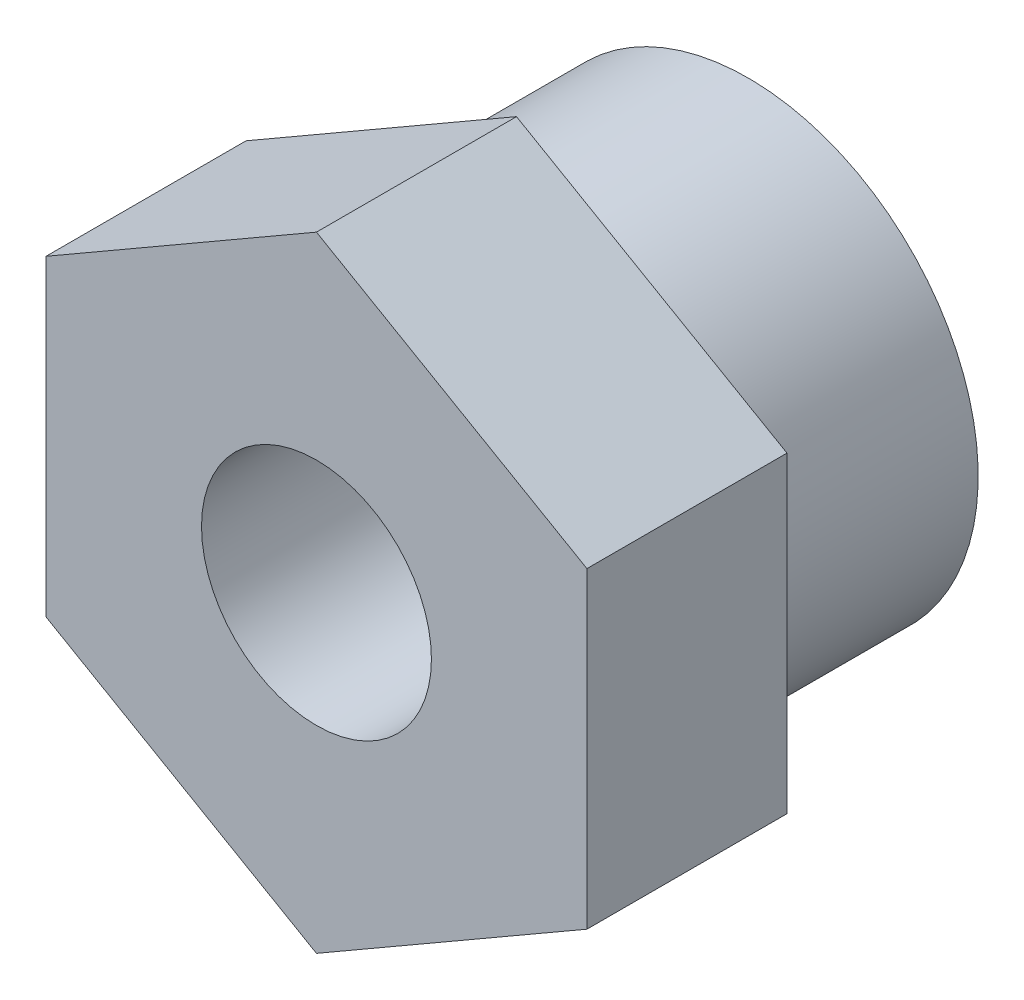
SolidWorks part; units mm, degrees
ref_plane "Piano frontale" through (0, 0, 0) normal (0, 0, 1) x (1, 0, 0)
ref_plane "Piano superiore" through (0, 0, 0) normal (0, 1, 0) x (1, 0, 0)
ref_plane "Piano destro" through (0, 0, 0) normal (1, 0, 0) x (0, 0, -1)
sketch "Schizzo1" plane through (0, 0, 0) normal (0, 0, 1) x (1, 0, 0)
  circle A0 centre (0, 0) radius 17.25
  dimension "D1" = 34.5
extrude "Estrusione-Estrusione1" add sketch "Schizzo1" along normal blind 23.85
sketch "Schizzo2" plane through (0, 0, 23.85) normal (0, 0, 1) x (1, 0, 0)
  line L1 (0, 17.25) -> (-14.9389, 8.625)
  line L2 (-14.9389, 8.625) -> (-14.9389, -8.625)
  line L3 (-14.9389, -8.625) -> (0, -17.25)
  line L4 (0, -17.25) -> (14.9389, -8.625)
  line L5 (14.9389, -8.625) -> (14.9389, 8.625)
  line L6 (14.9389, 8.625) -> (0, 17.25)
  circle A0 centre (0, 0) radius 14.9389 construction
  circle M1 centre (0, 0) radius 17.25
extrude "Taglio-Estrusione1" cut sketch "Schizzo2" against normal blind 11.05 contours L1 M1 | L2 M1 | L3 M1 | L4 M1 | L5 M1 | L6 M1 region at (7.9344, 13.7429, 23.85) region at (-7.9344, 13.7429, 23.85) region at (-15.8689, 0, 23.85) region at (15.8689, 0, 23.85) region at (-7.9344, -13.7429, 23.85) region at (7.9344, -13.7429, 23.85)
hole_wizard "Foro Ø25.5 (12.7)-1" positions "Schizzo3" profile "Schizzo4" hole size "Ø25.5" standard "ISO" end condition through all
sketch "Schizzo3" plane through (0, 0, 23.85) normal (0, 0, 1) x (1, 0, 0)
  point P0 (0, 0)
sketch "Schizzo4" plane through (0, 0, 23.85) normal (1, 0, 0) x (0, -1, 0)
  line L0 (0, 0) -> (0, 23.85)
  line L1 (0, 23.85) -> (6.35, 23.85)
  line L2 (6.35, 23.85) -> (6.35, 0)
  line L5 (6.35, 0) -> (0, 0)
  line L11 (0, -6.35) -> (0, 107.95) construction
  dimension "Thru Hole Dia." = 12.7
  dimension "Thru Hole Depth" = 23.85
sketch "Schizzo5" plane through (0, 0, 0) normal (0, 0, -1) x (-1, 0, 0)
  circle A0 centre (0, 0) radius 12.7
  circle M2 centre (0, 0) radius 17.25
  dimension "D1" = 25.4
extrude "Taglio-Estrusione2" cut sketch "Schizzo5" against normal blind 12.8 contours A0 M2 region at (16.7621, 0, 0)
cosmetic thread "Filettatura cosmetica1" parameters "D2"=20.588
